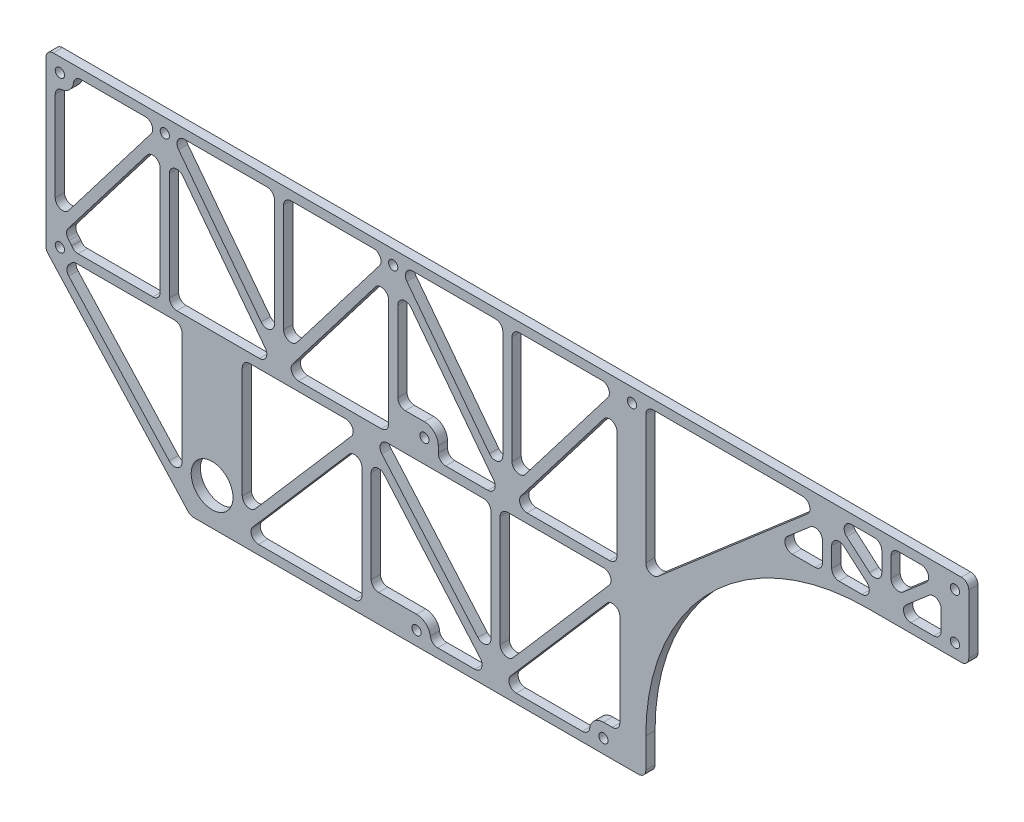
SolidWorks part; units mm, degrees
material "6061-T6 (SS)"
ref_plane "Front Plane" through (0, 0, 0) normal (0, 0, 1) x (1, 0, 0)
ref_plane "Top Plane" through (0, 0, 0) normal (0, 1, 0) x (1, 0, 0)
ref_plane "Right Plane" through (0, 0, 0) normal (1, 0, 0) x (0, 0, -1)
sketch "Sketch1" plane through (0, 0, 0) normal (0, 0, 1) x (1, 0, 0)
  line L1 (-317.5, 114.3) -> (317.5, 114.3)
  line L2 (-317.5, 114.3) -> (-317.5, -114.3)
  line L3 (-317.5, -114.3) -> (317.5, -114.3)
  line L4 (317.5, 114.3) -> (317.5, -114.3)
  line L5 (-317.5, 114.3) -> (317.5, -114.3) construction
  line L6 (-317.5, -114.3) -> (317.5, 114.3) construction
  circle A0 centre (206.8246, -88.9) radius 14.3891
  circle A1 centre (-203.2, -88.9) radius 14.3891
  point P0 (0, 0)
  dimension "D3" = 25.4
  dimension "D4" = 410.0246
  dimension "D5" = 28.7782
  dimension "D6" = 114.3
  dimension "D1" = 228.6
  dimension "D2" = 635
extrude "Boss-Extrude1" add sketch "Sketch1" along normal blind 6.35
sketch "Sketch2" plane through (0, 0, 6.35) normal (0, 0, 1) x (1, 0, 0)
  line L9 (-188.8109, -88.9) -> (192.4355, -88.9) construction
  line L17 (-311.15, -12.5845) -> (-311.15, -95.25)
  line L18 (-298.45, -107.95) -> (-223.9391, -107.95)
  line L19 (-223.9391, -107.95) -> (-311.15, -12.5845)
  line L20 (-317.5, -114.3) -> (317.5, -114.3) construction
  line L21 (-317.5, 114.3) -> (-317.5, -114.3) construction
  line L22 (-311.15, -3.175) -> (-223.9391, -98.5405)
  line L23 (-223.9391, -98.5405) -> (-223.9391, -3.175)
  line L24 (-223.9391, -3.175) -> (-311.15, -3.175)
  line L25 (-311.15, 107.95) -> (-311.15, 13.6197)
  line L31 (-96.9118, 0) -> (-96.9118, -114.3) construction
  line L38 (311.15, -11.3467) -> (311.15, -95.25)
  line L39 (298.45, -107.95) -> (227.5637, -107.95)
  line L40 (227.5637, -107.95) -> (311.15, -11.3467)
  line L41 (311.15, -1.642) -> (227.5637, -1.642)
  line L42 (227.5637, -1.642) -> (227.5637, -98.2453)
  line L43 (227.5637, -98.2453) -> (311.15, -1.642)
  line L44 (317.5, -114.3) -> (317.5, 114.3) construction
  line L45 (-317.5, 0) -> (49682.5, 0) construction
  line L70 (-311.15, 13.6197) -> (-238.9187, 107.95)
  line L71 (-238.9187, 107.95) -> (-311.15, 107.95)
  line L72 (-238.9187, 97.5053) -> (-311.15, 3.175)
  line L73 (-311.15, 3.175) -> (-238.9187, 3.175)
  line L74 (-238.9187, 3.175) -> (-238.9187, 97.5053)
  line L75 (317.5, 114.3) -> (-317.5, 114.3) construction
  line L76 (-160.3375, 3.175) -> (-232.5687, 3.175)
  line L77 (-232.5687, 97.5053) -> (-160.3375, 3.175)
  line L78 (-232.5687, 3.175) -> (-232.5687, 97.5053)
  line L79 (-160.3375, 13.6197) -> (-232.5687, 107.95)
  line L80 (-160.3375, 107.95) -> (-160.3375, 13.6197)
  line L81 (-232.5687, 107.95) -> (-160.3375, 107.95)
  line L88 (-235.7437, -1000) -> (-235.7437, 49000) construction
  line L119 (298.45, -104.775) -> (298.45, -107.95)
  line L120 (307.975, -95.25) -> (311.15, -95.25)
  line L121 (0, -923.8) -> (0, 49076.2) construction
  line L122 (-298.45, -104.775) -> (-298.45, -107.95)
  line L123 (-307.975, -95.25) -> (-311.15, -95.25)
  line L124 (-100.0868, -3.175) -> (-182.4609, -98.2525)
  line L125 (-182.4609, -107.95) -> (-100.0868, -107.95)
  line L126 (-182.4609, -98.2525) -> (-182.4609, -3.175)
  line L127 (-182.4609, -3.175) -> (-100.0868, -3.175)
  line L128 (-100.0868, -107.95) -> (-100.0868, -12.8725)
  line L129 (-182.4609, -107.95) -> (-100.0868, -12.8725)
  line L130 (-11.3627, -107.95) -> (-93.7368, -107.95)
  line L131 (-11.3627, -107.95) -> (-93.7368, -12.8725)
  line L132 (-93.7368, -107.95) -> (-93.7368, -12.8725)
  line L133 (-93.7368, -3.175) -> (-11.3627, -98.2525)
  line L134 (-11.3627, -3.175) -> (-93.7368, -3.175)
  line L135 (-11.3627, -98.2525) -> (-11.3627, -3.175)
  line L136 (-8.1877, 0) -> (-8.1877, -114.3) construction
  line L137 (-5.0127, -3.175) -> (77.3614, -3.175)
  line L138 (-5.0127, -98.2525) -> (-5.0127, -3.175)
  line L139 (77.3614, -3.175) -> (-5.0127, -98.2525)
  line L140 (-5.0127, -107.95) -> (77.3614, -12.8725)
  line L141 (77.3614, -107.95) -> (77.3614, -12.8725)
  line L142 (-5.0127, -107.95) -> (77.3614, -107.95)
  line L149 (83.7114, -3.175) -> (186.0855, -3.175)
  line L150 (186.0855, -3.175) -> (186.0855, -99.242)
  line L151 (186.0855, -99.242) -> (83.7114, -3.175)
  line L152 (83.7114, -11.883) -> (83.7114, -107.95)
  line L153 (83.7114, -107.95) -> (186.0855, -107.95)
  line L154 (186.0855, -107.95) -> (83.7114, -11.883)
  circle A0 centre (-203.2, -88.9) radius 14.3891 construction
  circle A1 centre (206.8246, -88.9) radius 14.3891 construction
  circle A2 centre (307.975, -104.775) radius 3.175
  arc A3 (298.45, -104.775) -> (307.975, -95.25) centre (307.975, -104.775) cw
  arc A4 (-298.45, -104.775) -> (-307.975, -95.25) centre (-307.975, -104.775) ccw
  circle A5 centre (-307.975, -104.775) radius 3.175
  circle A7 centre (206.8246, -88.9) radius 14.3891 construction
  point P42 (-317.5, 0)
  point P103 (0, 114.3)
  dimension "D3" = 20.7391
  dimension "D7" = 20.7391
  dimension "D11" = 20.7391
  dimension "D19" = 6.35
  dimension "D21" = 9.525
  dimension "D22" = 9.525
  dimension "D1" = 6.35
  dimension "D4" = 3.175
  dimension "D5" = 6.35
  dimension "D6" = 6.35
  dimension "D8" = 82.3741
  dimension "D9" = 6.35
  dimension "D10" = 6.35
  dimension "D12" = 3.175
  dimension "D13" = 6.35
  dimension "D14" = 6.35
  dimension "D15" = 6.35
  dimension "D16" = 72.2313
  dimension "D17" = 3.175
  dimension "D20" = 9.525
  dimension "D18" = 3.175
  dimension "D23" = 3.175
  dimension "D24" = 6.35
  dimension "D25" = 6.35
  dimension "D26" = 6.35
extrude "Cut-Extrude1" cut sketch "Sketch2" against normal through all
pattern_linear "LPattern2" count 4 spacing 157.1625 along (1, 0, 0) of face at (-275.0344, 3.175, 3.175) of face at (-275.0344, 60.7849, 3.175) of face at (-311.15, 60.7849, 3.175) of face at (-275.0344, 107.95, 3.175) of face at (-238.9188, 50.3401, 3.175) of face at (-275.0344, 50.3401, 3.175) of face at (-232.5687, 50.3401, 3.175) of face at (-196.4531, 3.175, 3.175) of face at (-196.4531, 60.7849, 3.175) of face at (-196.4531, 107.95, 3.175) of face at (-160.3375, 60.7849, 3.175) of face at (-196.4531, 50.3401, 3.175)
sketch "Sketch3" plane through (0, 0, 6.35) normal (0, 0, 1) x (1, 0, 0)
  line L0 (317.5, 114.3) -> (-317.5, 114.3) construction
  line L1 (-317.5, 114.3) -> (-317.5, -114.3) construction
  line L2 (-238.9187, 107.95) -> (-311.15, 107.95) construction
  line L3 (-311.15, 107.95) -> (-311.15, 13.6197) construction
  line L4 (-307.975, 95.25) -> (-311.15, 95.25)
  line L5 (-298.45, 104.775) -> (-298.45, 107.95)
  line L6 (-298.45, 107.95) -> (-311.15, 107.95)
  line L7 (-311.15, 107.95) -> (-311.15, 95.25)
  line L8 (0, -923.8) -> (0, 49076.2) construction
  line L9 (298.45, 107.95) -> (311.15, 107.95)
  line L10 (298.45, 104.775) -> (298.45, 107.95)
  line L11 (307.975, 95.25) -> (311.15, 95.25)
  line L12 (311.15, 107.95) -> (311.15, 95.25)
  circle A0 centre (-307.975, 104.775) radius 3.175
  arc A1 (-298.45, 104.775) -> (-307.975, 95.25) centre (-307.975, 104.775) cw
  circle A2 centre (307.975, 104.775) radius 3.175
  arc A3 (298.45, 104.775) -> (307.975, 95.25) centre (307.975, 104.775) ccw
  point P19 (0, 114.3)
  dimension "D1" = 6.35
  dimension "D4" = 9.525
  dimension "D2" = 9.525
  dimension "D3" = 9.525
extrude "Boss-Extrude2" add sketch "Sketch3" against normal up to surface (6.35 mm away) contours A1 L5 L6 A0 L7 L4 | L10 A3 L11 L12 A2 L9 | L9 A2 L12 | A0 L6 L7 region at (-304.5172, 101.3172, 6.35) region at (-310.4408, 107.2408, 6.35) region at (304.5172, 101.3172, 6.35) region at (310.4408, 107.2408, 6.35) up to face at (184.4146, 76.5066, 0)
sketch "Sketch4" plane through (0, 0, 0) normal (0, 0, -1) x (-1, 0, 0)
  line L0 (52.9336, -104.775) -> (52.9336, -114.3)
  line L1 (52.9336, -114.3) -> (100.0868, -114.3)
  line L2 (100.0868, -114.3) -> (100.0868, -95.25)
  line L3 (100.0868, -95.25) -> (62.4586, -95.25)
  line L4 (-56.5582, -104.775) -> (-56.5582, -114.3)
  line L5 (-56.5582, -114.3) -> (-83.7114, -114.3)
  line L6 (-83.7114, -114.3) -> (-83.7114, -95.25)
  line L7 (-83.7114, -95.25) -> (-66.0832, -95.25)
  line L8 (317.5, -114.3) -> (-317.5, -114.3) construction
  line L9 (-83.7114, -11.883) -> (-83.7114, -107.95) construction
  line L10 (100.0868, -107.95) -> (100.0868, -12.8725) construction
  circle A0 centre (-66.0832, -104.775) radius 3.175
  circle A2 centre (62.4586, -104.775) radius 3.175
  circle A3 centre (62.4586, -104.775) radius 3.175 construction
  arc A4 (52.9336, -104.775) -> (62.4586, -95.25) centre (62.4586, -104.775) cw
  arc A5 (-56.5582, -104.775) -> (-66.0832, -95.25) centre (-66.0832, -104.775) ccw
  circle A7 centre (-66.0832, -104.775) radius 3.175 construction
  dimension "D1" = 6.35
  dimension "D2" = 6.35
extrude "Boss-Extrude5" add sketch "Sketch4" against normal up to surface (6.35 mm away) contours L4 A5 L7 L6 L5 A0 | A4 L0 L1 L2 L3 A2 region at (-77.5285, -104.945, 0) region at (70.8883, -105.084, 0) up to face at (-304.8, 104.775, 6.35)
sketch "Sketch5" plane through (0, 0, 0) normal (0, 0, -1) x (-1, 0, 0)
  line L0 (-328.541, 8.7526) -> (-195.2509, -145.2949)
  line L1 (-195.2509, -145.2949) -> (-328.541, -145.2949)
  line L2 (-328.541, -145.2949) -> (-328.541, 8.7526)
  line L3 (-311.15, -11.3467) -> (-227.5637, -107.95) construction
  line L4 (209.5271, -123.7095) -> (340.2884, 19.2785)
  line L5 (340.2884, 19.2785) -> (340.2884, -123.7095)
  line L6 (340.2884, -123.7095) -> (209.5271, -123.7095)
  line L8 (223.9391, -107.95) -> (311.15, -12.5845) construction
extrude "Cut-Extrude2" cut sketch "Sketch5" against normal through all
sketch "Sketch6" plane through (0, 0, 0) normal (0, 0, -1) x (-1, 0, 0)
  line L0 (-275.0344, 3.175) -> (-275.0344, -1.642) construction
  line L1 (-238.9187, 3.175) -> (-311.15, 3.175) construction
  line L2 (-311.15, -1.642) -> (-227.5637, -1.642) construction
  line L3 (-1271.9719, 0.7665) -> (48728.0281, 0.7665) construction
  line L5 (-317.5, -4.0078) -> (-317.5, 114.3) construction
  line L7 (317.5, 114.3) -> (317.5, -5.6407) construction
  circle A0 centre (-307.975, 0.7665) radius 3.175
  circle A1 centre (307.975, 0.7665) radius 3.175
  circle A3 centre (-307.975, 0.7665) radius 9.525
  circle A4 centre (307.975, 0.7665) radius 9.525
  point P5 (-275.0344, 0.7665)
  dimension "D1" = 6.35
  dimension "D2" = 6.35
  dimension "D3" = 6.35
  dimension "D4" = 6.35
  dimension "D5" = 6.35
  dimension "D6" = 6.35
extrude "Boss-Extrude6" add sketch "Sketch6" against normal up to surface (6.35 mm away) contours A3 A0 | A1 region at (317.2306, 0.7665, 0) region at (-298.7194, 0.7665, 0) up to face at (0.6562, -1.6081, 6.35)
extrude "Cut-Extrude4" cut sketch "Sketch6<4>" against normal through all contours A1 | A0 region at (307.975, 0.7665, 0) region at (-307.975, 0.7665, 0)
sketch "Sketch6<4>" plane through (0, 0, 0) normal (0, 0, -1) x (-1, 0, 0) same geometry as "Sketch6"
fillet "Fillet1" radius 5.08 92 edges at (-311.15, 13.6197, 3.175) (-238.9187, 107.95, 3.175) (-223.9391, -98.5405, 3.175) (-223.9391, -3.175, 3.175) (227.5637, -1.642, 3.175) (227.5637, -98.2453, 3.175) (-232.5687, 107.95, 3.175) (-160.3375, 107.95, 3.175) (-160.3375, 13.6197, 3.175) (-238.9188, 97.5053, 3.175) (-238.9187, 3.175, 3.175) (-232.5687, 3.175, 3.175) (-232.5687, 97.5053, 3.175) (-160.3375, 3.175, 3.175) (-317.5, 114.3, 3.175) (317.5, 114.3, 3.175) (-153.9875, 13.6197, 3.175) (-153.9875, 107.95, 3.175) (-81.7563, 107.95, 3.175) (-153.9875, 3.175, 3.175) (-81.7563, 97.5053, 3.175) (-81.7563, 3.175, 3.175) (-75.4062, 3.175, 3.175) (-75.4062, 97.5053, 3.175) (-3.175, 3.175, 3.175) (-75.4062, 107.95, 3.175) (-3.175, 107.95, 3.175) (-3.175, 13.6197, 3.175) (3.175, 13.6197, 3.175) (3.175, 107.95, 3.175) (75.4062, 107.95, 3.175) (3.175, 3.175, 3.175) (75.4062, 97.5053, 3.175) (75.4062, 3.175, 3.175) (81.7563, 3.175, 3.175) (81.7563, 97.5053, 3.175) (153.9875, 3.175, 3.175) (81.7563, 107.95, 3.175) (153.9875, 107.95, 3.175) (153.9875, 13.6197, 3.175) (160.3375, 13.6197, 3.175) (160.3375, 107.95, 3.175) (232.5687, 107.95, 3.175) (160.3375, 3.175, 3.175) (232.5687, 97.5053, 3.175) (232.5687, 3.175, 3.175) (238.9187, 3.175, 3.175) (238.9187, 97.5053, 3.175) (-311.15, 95.25, 3.175) (-298.45, 107.95, 3.175) (311.15, 95.25, 3.175) (311.15, 13.6197, 3.175) (238.9187, 107.95, 3.175) (298.45, 107.95, 3.175) (-11.3627, -98.2525, 3.175) (-93.7368, -3.175, 3.175) (-11.3627, -3.175, 3.175) (-93.7368, -12.8725, 3.175) (-11.3627, -107.95, 3.175) (-182.4609, -107.95, 3.175) (-100.0868, -12.8725, 3.175) (-100.0868, -107.95, 3.175) (-182.4609, -98.2525, 3.175) (-100.0868, -3.175, 3.175) (77.3614, -12.8725, 3.175) (-5.0127, -107.95, 3.175) (186.0855, -3.175, 3.175) (186.0855, -99.242, 3.175) (83.7114, -3.175, 3.175) (83.7114, -11.883, 3.175) (77.3614, -3.175, 3.175) (-5.0127, -98.2525, 3.175) (-5.0127, -3.175, 3.175) (-182.4609, -3.175, 3.175) (77.3614, -95.25, 3.175) (56.5582, -107.95, 3.175) (-52.9336, -107.95, 3.175) (-93.7368, -95.25, 3.175) (222.0693, -114.3, 3.175) (317.5, -4.0078, 3.175) (-317.5, -5.6407, 3.175) (-218.1321, -114.3, 3.175) (298.7595, -1.642, 3.175) (305.3192, -8.3808, 3.175) (298.7595, 3.175, 3.175) (-298.7595, 3.175, 3.175) (-305.8794, 10.0581, 3.175) (-299.3038, -3.175, 3.175) (-306.197, -8.5911, 3.175) (305.8794, 10.0581, 3.175) (83.7114, -107.95, 3.175) (186.0855, -107.95, 3.175)
sketch "Sketch7" plane through (0, 0, 0) normal (0, 0, -1) x (-1, 0, 0)
  line L0 (-317.5, -2.1152) -> (-317.5, 109.22) construction
  line L1 (-317.5, 126.0608) -> (-95.25, 126.0608)
  line L2 (-317.5, 126.0608) -> (-317.5, -161.6476)
  line L3 (-317.5, -161.6476) -> (-95.25, -161.6476)
  line L4 (-95.25, 126.0608) -> (-95.25, -161.6476)
  dimension "D1" = 222.25
extrude "Cut-Extrude5" cut sketch "Sketch7" against normal through all
sketch "Sketch8" plane through (0, 0, 0) normal (0, 0, -1) x (-1, 0, 0)
  line L0 (215.8938, -114.3) -> (-95.25, -114.3) construction
  line L1 (-95.25, 114.3) -> (-81.7563, 114.3)
  line L2 (-95.25, 114.3) -> (-95.25, -114.3)
  line L3 (-95.25, -114.3) -> (-81.7562, -114.3)
  line L4 (-81.7563, 114.3) -> (-81.7562, -114.3)
  line L5 (-81.7563, 82.5153) -> (-81.7563, 8.255) construction
extrude "Boss-Extrude7" add sketch "Sketch8" against normal up to surface (6.35 mm away) up to face at (7.5982, 9.1299, 6.35)
sketch "Sketch9" plane through (0, 0, 0) normal (0, 0, -1) x (-1, 0, 0)
  line L1 (-95.25, 114.3) -> (312.42, 114.3) construction
  line L2 (-95.25, -114.3) -> (-95.25, 114.3) construction
  circle A0 centre (-85.725, 104.775) radius 3.175
  dimension "D1" = 6.35
  dimension "D2" = 6.35
  dimension "D3" = 6.35
extrude "Cut-Extrude6" cut sketch "Sketch9" against normal through all
fillet "Fillet2" radius 5.08 1 edges at (95.25, -114.3, 3.175)
sketch "Sketch12" plane through (0, 0, 0) normal (0, 0, -1) x (-1, 0, 0)
  line L0 (16.4427, -3.175) -> (82.6141, -3.175) construction
  line L1 (47.5691, -3.175) -> (66.6191, -3.175)
  line L2 (47.5691, -3.175) -> (47.5691, 12.7)
  line L3 (47.5691, 12.7) -> (66.6191, 12.7)
  line L4 (66.6191, -3.175) -> (66.6191, 12.7)
  line L5 (70.3262, 3.175) -> (13.4632, 3.175) construction
  line L6 (75.4062, 82.5153) -> (75.4062, 8.255) construction
  line L7 (47.5691, 3.175) -> (42.4891, 3.175)
  line L8 (57.0941, 22.225) -> (81.7563, 22.225)
  line L9 (81.7563, 8.255) -> (81.7563, 82.5153) construction
  line L10 (81.7563, 22.225) -> (81.7563, -3.175)
  line L11 (81.7563, -3.175) -> (66.6191, -3.175)
  line L12 (75.4062, 22.225) -> (75.4062, 27.305)
  circle A0 centre (57.0941, 12.7) radius 3.175
  circle A1 centre (57.0941, 12.7) radius 3.175 construction
  arc A2 (47.5691, 12.7) -> (66.6191, 12.7) centre (57.0941, 12.7) cw
  arc A4 (42.4891, 3.175) -> (47.5691, 8.255) centre (42.4891, 8.255) ccw
  arc A5 (70.3262, 22.225) -> (75.4062, 27.305) centre (70.3262, 27.305) ccw
  dimension "D1" = 6.35
  dimension "D2" = 10.16
  dimension "D3" = 10.16
extrude "Boss-Extrude8" add sketch "Sketch12" against normal up to surface (6.35 mm away) contours A0 L3 L2 L1 L4 | A2 L3 A0 | L4 | A4 L7 L2 | A5 L8 L12 region at (-57.0941, 4.3984, 0) region at (-73.7203, 10.0346, 0) region at (-46.4344, 4.3097, 0) region at (-57.0941, 17.0794, 0) region at (-74.2715, 23.3597, 0) up to face at (82.55, 104.775, 6.35)
sketch "Sketch13" plane through (0, 0, 0) normal (0, 0, -1) x (-1, 0, 0)
  line L0 (-95.25, -109.22) -> (-95.25, 114.3) construction
  line L1 (-317.5, 114.3) -> (-95.25, 114.3)
  line L2 (-317.5, 114.3) -> (-317.5, 63.5)
  line L3 (-317.5, 63.5) -> (-95.25, 63.5)
  line L4 (-95.25, 114.3) -> (-95.25, 63.5)
  line L5 (317.5, 63.5) -> (-317.5, 63.5) construction
  line L6 (-95.25, 63.5) -> (-95.25, -88.9)
  arc A2 (-95.25, -88.9) -> (-247.65, 63.5) centre (-247.65, -88.9) ccw
  point P11 (-196.85, -88.9)
extrude "Boss-Extrude9" add sketch "Sketch13" against normal up to surface (6.35 mm away) contours A2 L6 L3 | L4 L1 L2 L3 region at (206.375, 88.9, 0) region at (129.2913, 29.4587, 0) up to face at (-50.3746, 28.0405, 6.35)
sketch "Sketch14" plane through (0, 0, 0) normal (0, 0, -1) x (-1, 0, 0)
  line L3 (-317.5, 114.3) -> (312.42, 114.3) construction
  line L4 (-139.304, 27.1236) -> (-143.7941, 22.6335) construction
  line L5 (-216.8009, 99.5665) -> (-182.3264, 69.85)
  line L6 (-182.3264, 69.85) -> (-216.8009, 69.85)
  line L7 (-216.8009, 69.85) -> (-216.8009, 99.5665)
  line L8 (-317.5, 63.5) -> (-247.65, 63.5) construction
  line L9 (-298.45, 99.5665) -> (-298.45, 69.85)
  line L10 (-298.45, 69.85) -> (-263.9755, 69.85)
  line L11 (-263.9755, 69.85) -> (-298.45, 99.5665)
  line L12 (-298.45, 107.95) -> (-263.9755, 107.95)
  line L13 (-263.9755, 107.95) -> (-263.9755, 78.2335)
  line L14 (-263.9755, 78.2335) -> (-298.45, 107.95)
  line L15 (-317.5, 114.3) -> (-317.5, 63.5) construction
  line L16 (-260.8005, 114.3) -> (-260.8005, 63.5) construction
  line L17 (-223.1509, 69.85) -> (-257.6255, 69.85)
  line L18 (-223.1509, 99.5665) -> (-223.1509, 69.85)
  line L19 (-257.6255, 69.85) -> (-223.1509, 99.5665)
  line L20 (-257.6255, 107.95) -> (-257.6255, 78.2335)
  line L21 (-223.1509, 107.95) -> (-257.6255, 107.95)
  line L22 (-257.6255, 78.2335) -> (-223.1509, 107.95)
  line L23 (75.4062, 69.85) -> (81.7563, 69.85) construction
  line L24 (75.4062, 82.5153) -> (75.4062, 27.305) construction
  line L25 (81.7563, 8.255) -> (81.7563, 82.5153) construction
  line L26 (232.5687, 63.5) -> (238.9187, 63.5) construction
  line L27 (232.5687, 82.5153) -> (232.5687, 8.255) construction
  line L28 (238.9187, 8.255) -> (238.9187, 82.5153) construction
  line L29 (-216.8009, 107.95) -> (-95.25, 107.95)
  line L30 (-95.25, 107.95) -> (-95.25, 3.175)
  line L31 (-13.4632, 3.175) -> (-70.3262, 3.175) construction
  line L32 (-216.8009, 107.95) -> (-95.25, 3.175)
  circle A0 centre (-307.975, 104.775) radius 3.175
  circle A2 centre (-307.975, 73.025) radius 3.175
  arc A4 (-95.25, -88.9) -> (-247.65, 63.5) centre (-247.65, -88.9) ccw construction
  circle A6 centre (78.5812, 104.775) radius 3.175
  circle A7 centre (235.7437, 104.775) radius 3.175
  circle A9 centre (-85.725, 104.775) radius 3.175 construction
  point P47 (78.5812, 69.85)
  point P56 (235.7437, 63.5)
  dimension "D11" = 6.35
  dimension "D12" = 6.35
  dimension "D13" = 6.35
  dimension "D14" = 6.35
  dimension "D15" = 6.35
  dimension "D16" = 6.35
  dimension "D19" = 6.35
  dimension "D20" = 6.35
  dimension "D21" = 6.35
  dimension "D3" = 6.35
  dimension "D4" = 6.35
  dimension "D5" = 6.35
  dimension "D6" = 6.35
  dimension "D7" = 6.35
  dimension "D8" = 6.35
  dimension "D9" = 6.35
  dimension "D10" = 6.35
  dimension "D22" = 6.35
extrude "Cut-Extrude7" cut sketch "Sketch14" against normal through all contours L9 L10 L11 | A2 | L14 L13 L12 | A0 L14 | L14 A0 | L20 L22 L21 | L19 L17 L18 | L7 L6 L5 | A6 | A7 | L32 L30 L29 region at (205.3094, 79.7555, 0) region at (286.9585, 79.7555, 0) region at (275.467, 98.0445, 0) region at (234.6424, 79.7555, 0) region at (246.1339, 98.0445, 0) region at (307.975, 104.775, 0) region at (307.975, 73.025, 0) region at (-78.5812, 104.775, 0) region at (-235.7437, 104.775, 0)
fillet "Fillet3" radius 5.08 20 edges at (317.5, 114.3, 3.175) (317.5, 63.5, 3.175) (263.9755, 107.95, 3.175) (263.9755, 78.2335, 3.175) (257.6255, 107.95, 3.175) (257.6255, 78.2335, 3.175) (223.1509, 107.95, 3.175) (216.8009, 69.85, 3.175) (182.3264, 69.85, 3.175) (223.1509, 69.85, 3.175) (223.1509, 99.5665, 3.175) (216.8009, 99.5665, 3.175) (257.6255, 69.85, 3.175) (263.9755, 69.85, 3.175) (95.25, 3.175, 3.175) (95.25, 107.95, 3.175) (216.8009, 107.95, 3.175) (298.45, 107.95, 3.175) (298.45, 99.5665, 3.175) (298.45, 69.85, 3.175)
sketch "Sketch15" plane through (0, 0, 0) normal (0, 0, -1) x (-1, 0, 0)
  line L0 (-969.5377, 114.3) -> (49030.4623, 114.3) construction
  line L2 (-924.0391, -114.3) -> (49075.9609, -114.3) construction
  line L4 (-317.5, -916.3756) -> (-317.5, 49083.6244) construction
  line L6 (317.5, -926.5552) -> (317.5, 49073.4448) construction
  point P7 (-317.5, 114.3)
  point P9 (317.5, 114.3)
  point P10 (317.5, -114.3)
  point P11 (-317.5, -114.3)
